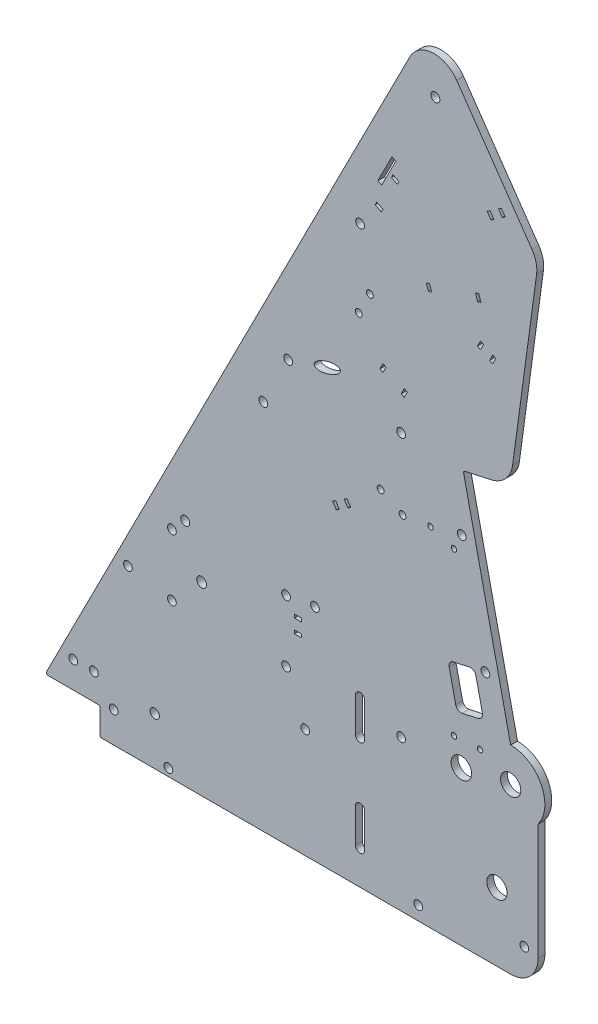
SolidWorks part; units mm, degrees
other "Markup1"
sketch "Sketch5"
ref_plane "Front Plane" through (0, 0, 0) normal (0, 0, 1) x (1, 0, 0)
ref_plane "Top Plane" through (0, 0, 0) normal (0, 1, 0) x (1, 0, 0)
ref_plane "Right Plane" through (0, 0, 0) normal (1, 0, 0) x (0, 0, -1)
sketch "Sketch1" plane through (0, 0, 0) normal (0, 0, 1) x (1, 0, 0)
  line L1 (228.6, -12.7) -> (228.6, 53.975)
  line L2 (178.7547, 351.4131) -> (0, 0)
  line L3 (228.6, 279.4) -> (178.7547, 351.4131)
  line L5 (0, 0) -> (25.4, 0)
  line L6 (25.4, 0) -> (25.4, -12.7)
  line L7 (25.4, -12.7) -> (228.6, -12.7)
  line L9 (215.9, 79.375) -> (193.9097, 178.5667)
  line L10 (193.9097, 178.5667) -> (215.6079, 183.377)
  line L11 (215.6079, 183.377) -> (228.6, 279.4)
  arc A0 (228.6, 53.975) -> (215.9, 79.375) centre (215.9, 63.5) ccw
  dimension "D7" = 12.7
  dimension "D8" = 76.2
  dimension "D10" = 31.75
  dimension "D2" = 292.1
  dimension "D3" = 25.4
  dimension "D4" = 215.9
  dimension "D5" = 394.2644
  dimension "D6" = 203.2
  dimension "D9" = 63.039
  dimension "D11" = 101.6
  dimension "D12" = 12.5
  dimension "D13" = 22.225
extrude "Boss-Extrude1" add sketch "Sketch1" along normal blind 3.175
sketch "Sketch2" plane through (0, 0, 3.175) normal (0, 0, 1) x (1, 0, 0)
  line L0 (178.7547, 351.4131) -> (0, 0) construction
  line L1 (25.4, -12.7) -> (228.6, -12.7) construction
  line L2 (215.9, 79.375) -> (193.9097, 178.5667) construction
  line L3 (193.9097, 178.5667) -> (215.6079, 183.377) construction
  line L4 (215.9, 79.375) -> (193.9097, 178.5667) construction
  line L5 (64.9432, 94.0578) -> (72.5445, 73.1732) construction
  line L6 (64.9432, 94.0578) -> (103.3734, 94.0578) construction
  line L10 (228.6, -12.7) -> (228.6, 53.975) construction
  circle A0 centre (64.9432, 94.0578) radius 2.0955
  circle A1 centre (180.975, 322.1643) radius 2.0955
  circle A2 centre (72.5445, 73.1732) radius 2.286
  circle A3 centre (193.2078, 152.3944) radius 2.032
  circle A4 centre (215.9, 63.5) radius 4.699
  circle A7 centre (173.0375, -6.35) radius 2.032
  circle A8 centre (204.203, 102.7985) radius 2.032
  circle A26 centre (209.55, 19.05) radius 4.699
  arc A30 (228.6, 53.975) -> (215.9, 79.375) centre (215.9, 63.5) ccw construction
  circle A31 centre (165.1, 179.3875) radius 2.032
  circle A35 centre (111.724, 87.4607) radius 2.032
  circle A36 centre (111.724, 58.8857) radius 2.032
  circle A37 centre (58.765, 58.8857) radius 2.032
  circle A38 centre (58.765, 87.4607) radius 2.032
  circle A39 centre (111.724, 58.8857) radius 1.905 construction
  circle A42 centre (111.724, 87.4607) radius 1.905 construction
  circle A43 centre (58.765, 58.8857) radius 1.905 construction
  circle A44 centre (58.765, 87.4607) radius 1.905 construction
  dimension "D3" = 4.191
  dimension "D5" = 4.191
  dimension "D9" = 4.572
  dimension "D20" = 9.398
  dimension "D23" = 9.398
  dimension "D18" = 4.064
  dimension "D26" = 4.064
  dimension "D14" = 4.064
  dimension "D10" = 4.064
  dimension "D2" = 15.24
  dimension "D6" = 15.24
  dimension "D7" = 22.225
  dimension "D21" = 44.45
  dimension "D22" = 6.35
  dimension "D19" = 160.3375
  dimension "D24" = 44.45
  dimension "D25" = 6.35
  dimension "D27" = 25.4
  dimension "D28" = 50.8
  dimension "D29" = 6.35
  dimension "D17" = 6.35
  dimension "D33" = 55.5625
  dimension "D15" = 114.3
  dimension "D4" = 180.975
  dimension "D8" = 70
extrude "Cut-Extrude1" cut sketch "Sketch2" against normal through all
sketch "Sketch7" plane through (0, 0, 3.175) normal (0, 0, 1) x (1, 0, 0)
  line L0 (146.05, 3.175) -> (146.05, 19.05) construction
  line L1 (143.891, 3.175) -> (143.891, 19.05)
  line L2 (148.209, 3.175) -> (148.209, 19.05)
  line L3 (146.05, 47.625) -> (146.05, 63.5) construction
  line L4 (143.891, 47.625) -> (143.891, 63.5)
  line L5 (148.209, 47.625) -> (148.209, 63.5)
  line L6 (25.4, -12.7) -> (228.6, -12.7) construction
  line L12 (228.6, -12.7) -> (228.6, 53.975) construction
  line L13 (25.4, -12.7) -> (228.6, -12.7) construction
  arc A0 (143.891, 3.175) -> (148.209, 3.175) centre (146.05, 3.175) ccw
  arc A1 (148.209, 19.05) -> (143.891, 19.05) centre (146.05, 19.05) ccw
  arc A2 (143.891, 47.625) -> (148.209, 47.625) centre (146.05, 47.625) ccw
  arc A3 (148.209, 63.5) -> (143.891, 63.5) centre (146.05, 63.5) ccw
  circle A8 centre (50.8, 9.525) radius 2.159
  point P2 (146.05, 11.1125)
  point P9 (146.05, 55.5625)
  dimension "D1" = 4.318
  dimension "D5" = 4.318
  dimension "D2" = 15.875
  dimension "D3" = 15.875
  dimension "D4" = 44.45
  dimension "D6" = 95.25
  dimension "D7" = 82.55
  dimension "D8" = 15.875
  dimension "D9" = 22.225
extrude "Cut-Extrude2" cut sketch "Sketch7" against normal through all
sketch "Sketch10" plane through (0, 0, 3.175) normal (0, 0, 1) x (1, 0, 0)
  circle A0 centre (120.65, 38.1) radius 2.032
  circle A1 centre (165.1, 57.15) radius 2.032
  circle A2 centre (13.0465, 12.3347) radius 2.032
  circle A3 centre (22.5715, 12.3347) radius 2.032
  circle A4 centre (38.3604, 62.564) radius 2.032
  circle A5 centre (13.0465, 12.3347) radius 2.032 construction
  circle A6 centre (22.5715, 12.3347) radius 2.032 construction
  dimension "D1" = 4.064
  dimension "D3" = 38.1
  dimension "D2" = 120.65
  dimension "D4" = 63.5
  dimension "D5" = 69.85
extrude "Cut-Extrude3" cut sketch "Sketch10" against normal up to next
fillet "Fillet1" radius 12.7 4 edges at (228.6, -12.7, 1.5875) (178.7547, 351.4131, 1.5875) (215.6079, 183.377, 1.5875) (228.6, 279.4, 1.5875)
fillet "Fillet2" radius 0.7937 4 edges at (25.4, -12.7, 1.5875) (25.4, 0, 1.5875) (193.9097, 178.5667, 1.5875) (0, 0, 1.5875)
sketch "Sketch12" plane through (0, 0, 3.175) normal (0, 0, 1) x (1, 0, 0)
  circle A0 centre (31.75, 1.5875) radius 2.032
  circle A1 centre (173.0375, -6.35) radius 2.032
  circle A2 centre (222.25, 1.5875) radius 2.032
  circle A3 centre (57.15, -9.2075) radius 2.032
  circle A4 centre (57.15, -9.2075) radius 2.286 construction
  dimension "D1" = 4.064
  dimension "D2" = 4.064
extrude "Cut-Extrude5" cut sketch "Sketch12" against normal through all
sketch "Sketch13" plane through (0, 0, 3.175) normal (0, 0, 1) x (1, 0, 0)
  line L1 (228.6, 0) -> (228.6, 53.975) construction
  line L2 (1.2943, 0) -> (24.6062, 0) construction
  line L3 (26.1937, -12.7) -> (215.9, -12.7) construction
  line L8 (178.2697, 245.9923) -> (176.7582, 245.5069)
  line L9 (179.2404, 242.9693) -> (178.2697, 245.9923)
  line L10 (177.7289, 242.4839) -> (179.2404, 242.9693)
  line L11 (176.7582, 245.5069) -> (177.7289, 242.4839)
  line L12 (178.2697, 245.9923) -> (176.7582, 245.5069)
  line L13 (179.2404, 242.9693) -> (178.2697, 245.9923)
  line L14 (177.7289, 242.4839) -> (179.2404, 242.9693)
  line L15 (176.7582, 245.5069) -> (177.7289, 242.4839)
  line L16 (160.8477, 288.1984) -> (154.2836, 275.294)
  line L17 (200.6096, 249.8308) -> (202.1211, 250.3161)
  line L18 (199.639, 252.8538) -> (200.6096, 249.8308)
  line L19 (201.1505, 253.3391) -> (199.639, 252.8538)
  line L20 (202.1211, 250.3161) -> (201.1505, 253.3391)
  line L21 (200.6096, 249.8308) -> (202.1211, 250.3161)
  line L22 (199.639, 252.8538) -> (200.6096, 249.8308)
  line L23 (201.1505, 253.3391) -> (199.639, 252.8538)
  line L24 (202.1211, 250.3161) -> (201.1505, 253.3391)
  line L25 (160.8477, 288.1984) -> (162.6303, 287.2917)
  line L26 (160.5905, 279.7801) -> (163.4204, 278.3406)
  line L27 (161.3102, 281.1951) -> (160.5905, 279.7801)
  line L28 (164.1402, 279.7556) -> (161.3102, 281.1951)
  line L29 (163.4204, 278.3406) -> (164.1402, 279.7556)
  line L30 (160.5905, 279.7801) -> (163.4204, 278.3406)
  line L31 (161.3102, 281.1951) -> (160.5905, 279.7801)
  line L32 (164.1402, 279.7556) -> (161.3102, 281.1951)
  line L33 (163.4204, 278.3406) -> (164.1402, 279.7556)
  line L34 (154.2836, 275.294) -> (156.0662, 274.3872)
  line L35 (162.6303, 287.2917) -> (156.0662, 274.3872)
  line L36 (153.7897, 266.4104) -> (153.0699, 264.9954)
  line L37 (156.6196, 264.9709) -> (153.7897, 266.4104)
  line L38 (155.8998, 263.5559) -> (156.6196, 264.9709)
  line L39 (153.0699, 264.9954) -> (155.8998, 263.5559)
  line L40 (153.7897, 266.4104) -> (153.0699, 264.9954)
  line L41 (156.6196, 264.9709) -> (153.7897, 266.4104)
  line L42 (155.8998, 263.5559) -> (156.6196, 264.9709)
  line L43 (153.0699, 264.9954) -> (155.8998, 263.5559)
  line L110 (153.9925, 274.7218) -> (157.3929, 281.4066) construction
  line L111 (155.7751, 273.815) -> (159.1755, 280.4999) construction
  line L122 (203.3303, 234.0299) -> (201.9154, 234.7497)
  line L123 (201.8908, 231.2) -> (203.3303, 234.0299)
  line L124 (200.4759, 231.9198) -> (201.8908, 231.2)
  line L125 (201.9154, 234.7497) -> (200.4759, 231.9198)
  line L126 (203.3303, 234.0299) -> (201.9154, 234.7497)
  line L127 (201.8908, 231.2) -> (203.3303, 234.0299)
  line L128 (200.4759, 231.9198) -> (201.8908, 231.2)
  line L129 (201.9154, 234.7497) -> (200.4759, 231.9198)
  line L130 (206.1357, 229.0407) -> (207.5507, 228.321)
  line L131 (207.5752, 231.8707) -> (206.1357, 229.0407)
  line L132 (208.9902, 231.1509) -> (207.5752, 231.8707)
  line L133 (207.5507, 228.321) -> (208.9902, 231.1509)
  line L134 (206.1357, 229.0407) -> (207.5507, 228.321)
  line L135 (207.5752, 231.8707) -> (206.1357, 229.0407)
  line L136 (208.9902, 231.1509) -> (207.5752, 231.8707)
  line L137 (207.5507, 228.321) -> (208.9902, 231.1509)
  line L138 (211.5405, 292.889) -> (210.2352, 291.9855)
  line L139 (213.3475, 290.2784) -> (211.5405, 292.889)
  line L140 (212.0422, 289.3749) -> (213.3475, 290.2784)
  line L141 (210.2352, 291.9855) -> (212.0422, 289.3749)
  line L142 (211.5405, 292.889) -> (210.2352, 291.9855)
  line L143 (213.3475, 290.2784) -> (211.5405, 292.889)
  line L144 (212.0422, 289.3749) -> (213.3475, 290.2784)
  line L145 (210.2352, 291.9855) -> (212.0422, 289.3749)
  line L146 (206.3193, 289.275) -> (205.014, 288.3715)
  line L147 (208.1263, 286.6644) -> (206.3193, 289.275)
  line L148 (206.821, 285.7609) -> (208.1263, 286.6644)
  line L149 (205.014, 288.3715) -> (206.821, 285.7609)
  line L150 (206.3193, 289.275) -> (205.014, 288.3715)
  line L151 (208.1263, 286.6644) -> (206.3193, 289.275)
  line L152 (206.821, 285.7609) -> (208.1263, 286.6644)
  line L153 (205.014, 288.3715) -> (206.821, 285.7609)
  line L184 (133.3504, 136.102) -> (135.0815, 133.4404)
  line L185 (133.3504, 136.102) -> (134.6812, 136.9675)
  line L186 (135.0815, 133.4404) -> (136.4123, 134.3059)
  line L187 (155.2281, 200.1197) -> (156.643, 199.3999)
  line L188 (156.6676, 202.9496) -> (155.2281, 200.1197)
  line L189 (158.0826, 202.2298) -> (156.6676, 202.9496)
  line L190 (156.643, 199.3999) -> (158.0826, 202.2298)
  line L191 (155.2281, 200.1197) -> (156.643, 199.3999)
  line L192 (156.6676, 202.9496) -> (155.2281, 200.1197)
  line L193 (158.0826, 202.2298) -> (156.6676, 202.9496)
  line L194 (156.643, 199.3999) -> (158.0826, 202.2298)
  line L195 (134.6812, 136.9675) -> (136.4123, 134.3059)
  line L196 (165.1328, 195.0814) -> (166.5478, 194.3617)
  line L197 (166.5723, 197.9113) -> (165.1328, 195.0814)
  line L198 (167.9873, 197.1916) -> (166.5723, 197.9113)
  line L199 (166.5478, 194.3617) -> (167.9873, 197.1916)
  line L200 (165.1328, 195.0814) -> (166.5478, 194.3617)
  line L201 (166.5723, 197.9113) -> (165.1328, 195.0814)
  line L202 (167.9873, 197.1916) -> (166.5723, 197.9113)
  line L203 (166.5478, 194.3617) -> (167.9873, 197.1916)
  line L204 (140.4047, 136.9025) -> (138.6737, 139.5641)
  line L205 (140.4047, 136.9025) -> (141.7355, 137.768)
  line L206 (138.6737, 139.5641) -> (140.0045, 140.4296)
  line L207 (141.7355, 137.768) -> (140.0045, 140.4296)
  line L209 (169.1053, 332.4434) -> (0.5868, 1.1536) construction
  line L210 (88.0466, 102.1523) -> (85.2167, 103.5918) construction
  line L288 (115.661, 81.8727) -> (118.836, 81.8727)
  line L289 (115.661, 81.8727) -> (115.661, 80.2852)
  line L290 (118.836, 81.8727) -> (118.836, 80.2852)
  line L291 (115.661, 80.2852) -> (118.836, 80.2852)
  line L292 (115.661, 75.5227) -> (118.836, 75.5227)
  line L293 (115.661, 75.5227) -> (115.661, 73.9352)
  line L294 (118.836, 75.5227) -> (118.836, 73.9352)
  line L295 (115.661, 73.9352) -> (118.836, 73.9352)
  line L297 (115.661, 86.2542) -> (115.661, 60.0922) construction
  line L298 (59.9715, 91.3977) -> (110.5175, 91.3977) construction
  circle A0 centre (112.7125, 182.5625) radius 2.032
  circle A1 centre (146.05, 254) radius 2.032
  circle A2 centre (101.1964, 159.9231) radius 2.032 construction
  circle A3 centre (101.1964, 159.9231) radius 2.032
  circle A4 centre (145.4254, 217.7376) radius 1.6 construction
  circle A5 centre (150.594, 227.8985) radius 1.6 construction
  circle A7 centre (145.4254, 217.7376) radius 1.6
  circle A8 centre (150.594, 227.8985) radius 1.6
  circle A9 centre (155.5984, 151.9149) radius 1.6 construction
  circle A10 centre (165.7594, 146.7463) radius 1.6 construction
  circle A11 centre (155.5984, 151.9149) radius 1.6
  circle A12 centre (165.7594, 146.7463) radius 1.6
  ellipse E0 centre (130.8261, 188.4615) end of major axis (136.864, 190.4279) minor radius 2.3812 construction
  ellipse E1 centre (130.8261, 188.4615) end of major axis (136.864, 190.4279) minor radius 2.3812
  dimension "D2" = 4.064
  dimension "D5" = 4.064
  dimension "D1" = 195.2625
  dimension "D3" = 82.55
  dimension "D4" = 254
  dimension "D6" = 115.8875
  dimension "D11" = 7.62
  dimension "D12" = 6.858
  dimension "D13" = 1.5875
  dimension "D14" = 3.175
  dimension "D15" = 4.7625
  dimension "D16" = 60
  dimension "D17" = 57.15
  dimension "D24" = 50.8
  dimension "D29" = 3.175
  dimension "D30" = 1.5875
  dimension "D31" = 4.7625
  dimension "D32" = 0
  dimension "D33" = 9.525
  dimension "D7" = 0
  dimension "D8" = 0
  dimension "D9" = 0
  dimension "D10" = 0
  dimension "D18" = 0
  dimension "D19" = 0
  dimension "D20" = 0
  dimension "D21" = 0
  dimension "D22" = 0
  dimension "D23" = 0
extrude "Cut-Extrude6" cut sketch "Sketch13" against normal through all
sketch "Sketch14" plane through (0, 0, 3.175) normal (0, 0, 1) x (1, 0, 0)
  line L5 (186.8444, 98.9502) -> (199.2434, 101.699)
  line L6 (186.8444, 98.9502) -> (190.9676, 80.3518)
  line L7 (190.9676, 80.3518) -> (203.3665, 83.1006)
  line L8 (199.2434, 101.699) -> (203.3665, 83.1006)
  line L14 (202.8168, 85.5804) -> (199.7931, 99.2192) construction
  line L15 (193.4474, 80.9015) -> (200.8868, 82.5508) construction
  line L16 (187.3942, 96.4704) -> (190.4178, 82.8316) construction
  line L17 (196.7636, 101.1493) -> (189.3242, 99.5) construction
  circle A0 centre (189.6022, 69.9806) radius 1.27
  circle A1 centre (201.7089, 70.5092) radius 1.27
  circle A2 centre (189.6022, 69.9806) radius 1.27 construction
  circle A3 centre (201.7089, 70.5092) radius 1.27 construction
  circle A4 centre (165.1, 57.15) radius 2.032
  circle A5 centre (125.1498, 89.5229) radius 2.032
  circle A6 centre (178.7216, 148.5324) radius 1.27
  circle A8 centre (178.7216, 148.5324) radius 1.27 construction
  circle A9 centre (189.6226, 145.0954) radius 1.27
  circle A10 centre (189.6226, 145.0954) radius 1.27 construction
  point P8 (152.4, 88.9)
  dimension "D1" = 4.064
extrude "Cut-Extrude7" cut sketch "Sketch14" against normal through all both and the other way through all
fillet "Fillet3" radius 2.54 4 edges at (199.2434, 101.699, 1.5875) (186.8444, 98.9502, 1.5875) (190.9676, 80.3518, 1.5875) (203.3665, 83.1006, 1.5875)
sketch "Sketch15" plane through (0, 0, 3.175) normal (0, 0, 1) x (1, 0, 0)
  circle A0 centre (193.04, 58.801) radius 4.7625 construction
  circle A1 centre (193.04, 58.801) radius 4.7625
extrude "Cut-Extrude8" cut sketch "Sketch15" against normal through all
equation "\"D6@Sketch2\"=\"D2@Sketch2\""
